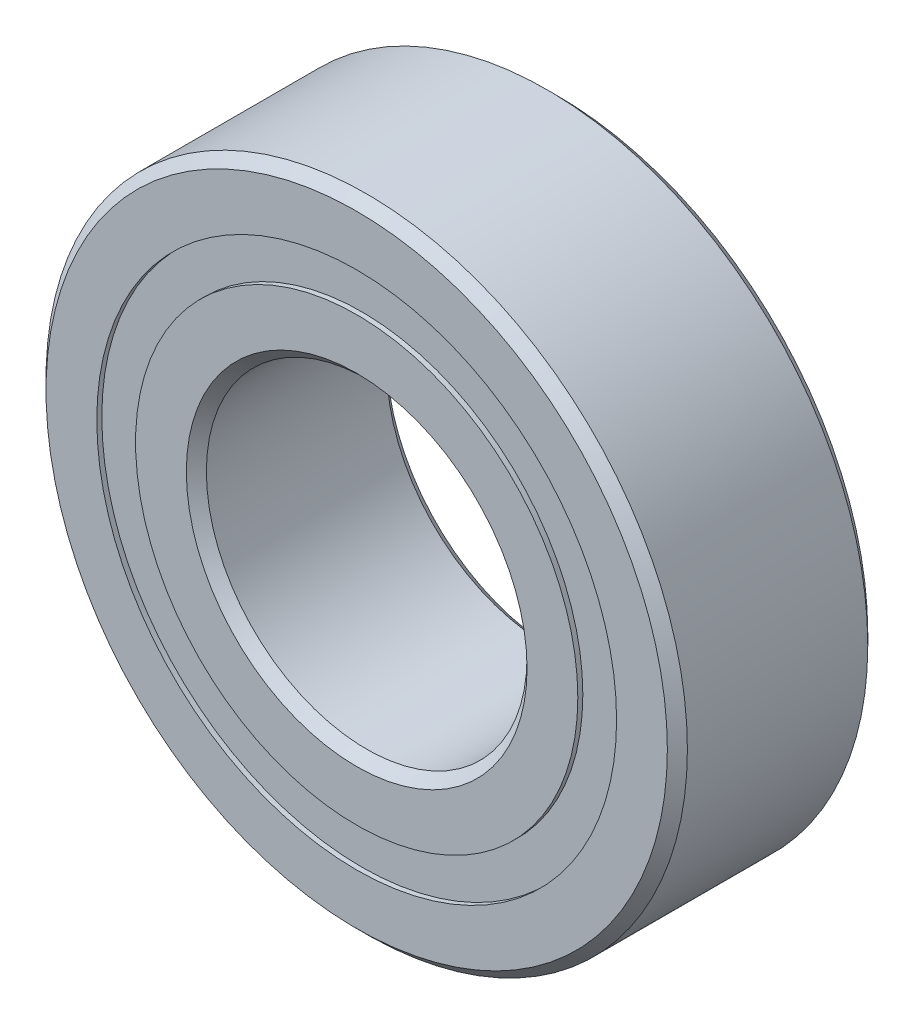
SolidWorks part; units mm, degrees
material "AISI 1020"
ref_plane "Front Plane" through (0, 0, 0) normal (0, 0, 1) x (1, 0, 0)
ref_plane "Top Plane" through (0, 0, 0) normal (0, 1, 0) x (1, 0, 0)
ref_plane "Right Plane" through (0, 0, 0) normal (1, 0, 0) x (0, 0, -1)
sketch "Sketch1" plane through (0, 0, 0) normal (1, 0, 0) x (0, 0, -1)
  line L0 (-2.5, 0) -> (2.5, 0) construction
  line L1 (0, 8) -> (0, -8) construction
  line L2 (2.25, 8) -> (-2.25, 8)
  line L3 (-2.25, 8) -> (-2.5, 7.75)
  line L4 (-2.5, 7.75) -> (-2.5, 6.4835)
  line L5 (-2.5, 6.4835) -> (-1.1111, 6.4835)
  line L6 (2.5, 6.4835) -> (1.1111, 6.4835)
  line L7 (2.5, 7.75) -> (2.5, 6.4835)
  line L8 (2.25, 8) -> (2.5, 7.75)
  line L9 (0, 8) -> (0, 6) construction
  line L10 (0, 6) -> (0, 4) construction
  arc A0 (-1.1111, 6.4835) -> (1.1111, 6.4835) centre (0, 6) cw
  point P14 (0, 4)
  dimension "D3" = 2.2222
  dimension "D1" = 45
  dimension "Width" = 5
  dimension "OD" = 16
  dimension "D2" = 0.25
  dimension "Shaft Dia" = 8
  dimension "D4" = 0.4835
revolve "Revolve1" add sketch "Sketch1" angle 360 about L0
sketch "Sketch3" plane through (0, 0, 0) normal (1, 0, 0) x (0, 0, -1)
  line L0 (-2.5, 5.5165) -> (-1.1111, 5.5165)
  line L1 (0, 8) -> (0, -8) construction
  line L2 (-2.5, 7.75) -> (-2.5, 6.4835) construction
  line L3 (-2.5, 5.5165) -> (-2.5, 4.25)
  line L4 (-2.25, 8) -> (-2.5, 7.75) construction
  line L5 (-2.5, 4.25) -> (-2.25, 4)
  line L6 (-2.25, 4) -> (2.25, 4)
  line L7 (2.25, 8) -> (2.25, -8) construction
  line L8 (2.25, 4) -> (2.5, 4.25)
  line L9 (2.5, -7.75) -> (2.5, 7.75) construction
  line L10 (2.5, 4.25) -> (2.5, 5.5165)
  line L11 (2.5, 5.5165) -> (1.1111, 5.5165)
  line L13 (2.25, 8) -> (2.5, 7.75) construction
  arc A0 (1.1111, 6.4835) -> (-1.1111, 6.4835) centre (0, 6) ccw construction
  arc A1 (1.1111, 5.5165) -> (-1.1111, 5.5165) centre (0, 6) cw
revolve "Revolve3" add sketch "Sketch3" angle 360 about L0
sketch "Sketch4" plane through (0, 0, 0) normal (1, 0, 0) x (0, 0, -1)
  line L0 (-1.2118, 6) -> (1.2118, 6)
  arc A2 (-1.2118, 6) -> (1.2118, 6) centre (0, 6) cw
  arc A3 (1.1111, 6.4835) -> (-1.1111, 6.4835) centre (0, 6) ccw construction
revolve "Revolve4" add sketch "Sketch4" angle 360 about L0
ref_axis "Axis1" through (0, 0, -2.5) along (0, 0, 1)
pattern_circular "CirPattern1" count 12 every 30 about axis through (0, 0, -2.5) along (0, 0, 1) of bodies 104
sketch "Sketch5" plane through (0, 0, 0) normal (1, 0, 0) x (0, 0, -1)
  line L0 (-2.5, 6.4835) -> (-1.1111, 6.4835) construction
  line L1 (-2.375, 6.4835) -> (-1.2118, 6.4835)
  line L2 (-2.375, 6.4835) -> (-2.375, 5.5165)
  line L3 (-2.375, 5.5165) -> (-1.2118, 5.5165)
  line L4 (-1.2118, 6.4835) -> (-1.2118, 5.5165)
  line L5 (-2.5, 5.5165) -> (-1.1111, 5.5165) construction
  line L6 (2.5, 6.4835) -> (1.1111, 6.4835) construction
  line L7 (2.375, 6.4835) -> (1.2118, 6.4835)
  line L8 (2.375, 6.4835) -> (2.375, 5.5165)
  line L9 (2.375, 5.5165) -> (1.2118, 5.5165)
  line L10 (1.2118, 6.4835) -> (1.2118, 5.5165)
  line L11 (2.5, 5.5165) -> (1.1111, 5.5165) construction
  line L12 (-2.25, 8) -> (-2.5, 7.75) construction
  point P18 (-2.375, 7.875)
revolve "Revolve5" add sketch "Sketch5" angle 360 about L0
sketch "Sketch6" plane through (0, 0, 0) normal (1, 0, 0) x (0, 0, -1)
  line L0 (2.5, 0) -> (-2.5, 0) construction
  line L1 (2.5, 6.4835) -> (1.7126, 6.4835)
  line L2 (2.5, 6.4835) -> (2.5, 6.9469)
  line L3 (2.5, 6.9469) -> (1.7126, 6.9469)
  line L4 (1.7126, 6.4835) -> (1.7126, 6.9469)
  dimension "Th" = 0.7874
  dimension "Flange OD" = 13.8938
revolve "Revolve6" [suppressed] add sketch "Sketch6" angle 360 about L0
equation "\"D2@Sketch1\" = \"Width@Sketch1\"*.05"
equation "\"D3@Sketch1\" = \"Width@Sketch1\"/2.25"
equation "\"D4@Sketch1\" = (((\"OD@Sketch1\"-\"Width@Sketch1\")/2)/3.25)/3.5"
equation "\"D2@CirPattern1\" = 360/\"Balls@CirPattern1\""
